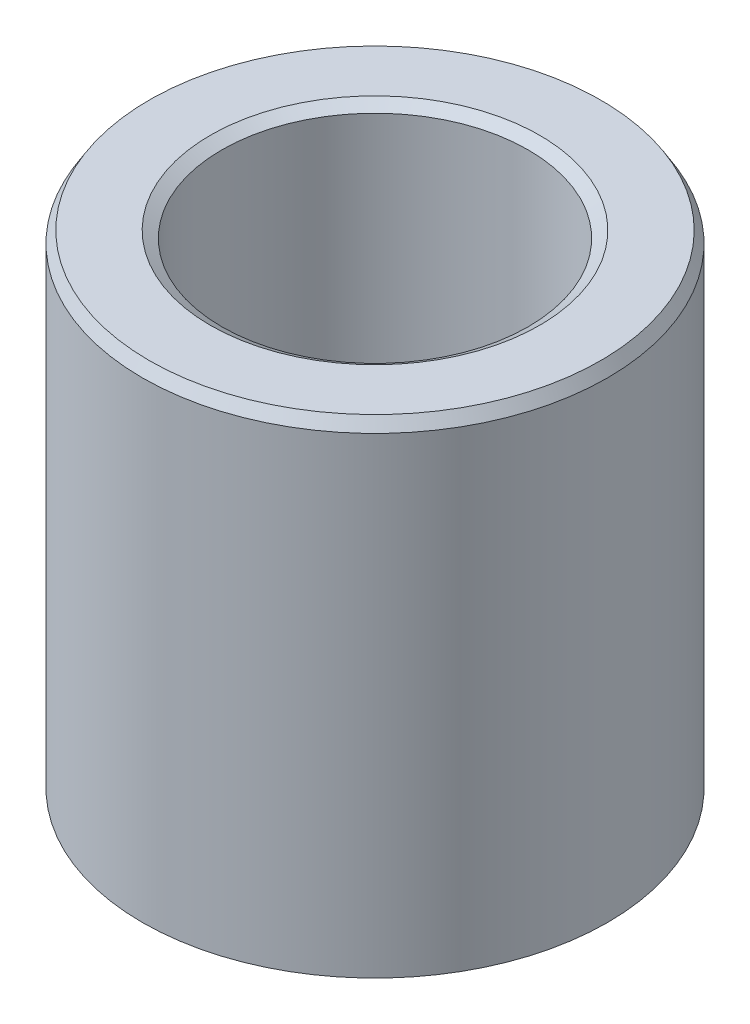
SolidWorks part; units mm, degrees
ref_plane "Front Plane" through (0, 0, 0) normal (0, 0, 1) x (1, 0, 0)
ref_plane "Top Plane" through (0, 0, 0) normal (0, 1, 0) x (1, 0, 0)
ref_plane "Right Plane" through (0, 0, 0) normal (1, 0, 0) x (0, 0, -1)
sketch "Sketch1" plane through (0, 0, 0) normal (0, 1, 0) x (1, 0, 0)
  circle A0 centre (0, 0) radius 50
  dimension "SLEEVE_OD" = 100
extrude "Boss-Extrude1" add sketch "Sketch1" along normal blind 105.3204
sketch "Sketch2" plane through (0, 0, 0) normal (0, 1, 0) x (1, 0, 0)
  circle A0 centre (0, 0) radius 32.9293
  dimension "BORE_D" = 65.8585
extrude "Cut-Extrude1" cut sketch "Sketch2" along normal through all
chamfer "Chamfer1" distance 2.4566 angle 31.31 4 edges at (0, 105.3204, 32.9293) (0, 0, 32.9293) (0, 0, 50) (0, 105.3204, 50) first distance on face at (0, 105.3204, 32.9293) first distance on face at (0, 0, 32.9293) first distance on face at (0, 105.3204, 50)
